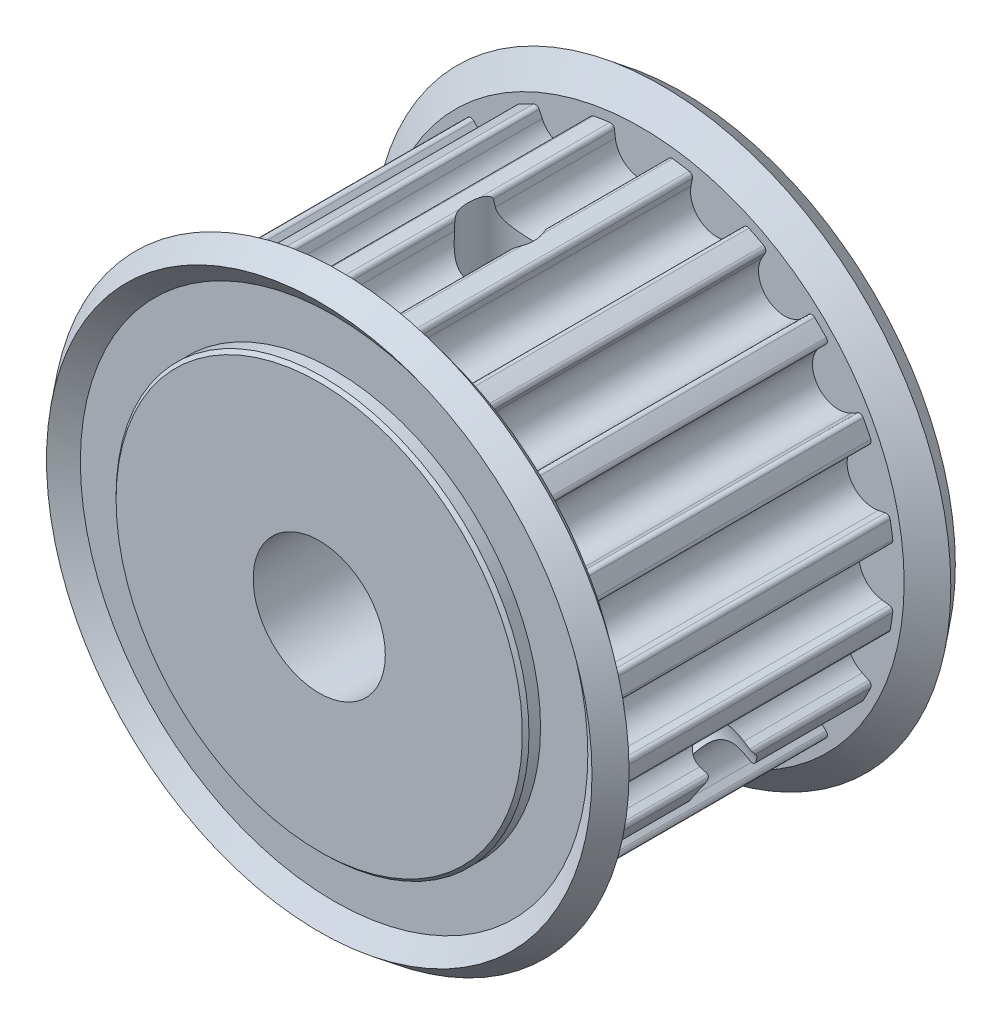
SolidWorks part; units mm, degrees
ref_plane "前视基准面" through (0, 0, 0) normal (0, 0, 1) x (1, 0, 0)
ref_plane "上视基准面" through (0, 0, 0) normal (0, 1, 0) x (1, 0, 0)
ref_plane "右视基准面" through (0, 0, 0) normal (1, 0, 0) x (0, 0, -1)
sketch "草图1" plane through (0, 0, 0) normal (1, 0, 0) x (0, 0, -1)
  line L0 (-34.7811, 0) -> (33.6192, 0) construction
  line L1 (0, 52.9736) -> (0, -62.0281) construction
  line L2 (-8.5, 15.345) -> (-8.5, 15.915)
  line L3 (-8.5, 15.915) -> (-9.7397, 17.5)
  line L4 (-9.7397, 17.5) -> (-11, 16.5143)
  line L5 (-11, 16.5143) -> (-10.1, 15.3636)
  line L6 (-10.1, 15.3636) -> (-10.1, 12.5)
  line L7 (-10.1, 12.5) -> (-11, 12.5)
  line L8 (10.1, 12.5) -> (11, 12.5)
  line L9 (10.1, 15.3636) -> (10.1, 12.5)
  line L10 (11, 16.5143) -> (10.1, 15.3636)
  line L11 (9.7397, 17.5) -> (11, 16.5143)
  line L12 (8.5, 15.915) -> (9.7397, 17.5)
  line L13 (8.5, 15.345) -> (8.5, 15.915)
  line L14 (8.5, -15.345) -> (8.5, -15.915)
  line L15 (8.5, -15.915) -> (9.7397, -17.5)
  line L16 (9.7397, -17.5) -> (11, -16.5143)
  line L17 (11, -16.5143) -> (10.1, -15.3636)
  line L18 (10.1, -15.3636) -> (10.1, -12.5)
  line L19 (10.1, -12.5) -> (11, -12.5)
  line L20 (-10.1, -12.5) -> (-11, -12.5)
  line L21 (-10.1, -15.3636) -> (-10.1, -12.5)
  line L22 (-11, -16.5143) -> (-10.1, -15.3636)
  line L23 (-9.7397, -17.5) -> (-11, -16.5143)
  line L24 (-8.5, -15.915) -> (-9.7397, -17.5)
  line L25 (-8.5, -15.345) -> (-8.5, -15.915)
  line L26 (-11, 12.5) -> (-11, -12.5)
  line L27 (11, 12.5) -> (11, -12.5)
  line L28 (-8.5, 15.345) -> (8.5, 15.345)
  line L29 (-8.5, -15.345) -> (8.5, -15.345)
  point P33 (0, 15.345)
  dimension "D1" = 2.5
  dimension "F" = 35
  dimension "D2" = 1.6
  dimension "E" = 25
  dimension "D3" = 1.6
  dimension "W" = 22
  dimension "D4" = 31.83
  dimension "A" = 17
  dimension "D5" = 30.69
sketch "草图2" plane through (0, 0, 0) normal (0, 0, 1) x (1, 0, 0)
  line L0 (-18.7064, 0) -> (19.5832, 0) construction
  line L1 (0, 30.5033) -> (0, -25.8377) construction
  line L2 (0, 0) -> (0, 15.345) construction
  line L3 (1.5718, 14.5756) -> (1.625, 15.0088)
  line L7 (0, 52.9736) -> (0, -62.0281) construction
  line L8 (-1.5, 3.7081) -> (-1.5, 5.4)
  line L9 (1.5, 3.7081) -> (1.5, 5.4)
  line L10 (-1.5, 5.4) -> (1.5, 5.4)
  line L11 (-1.5718, 14.5756) -> (-1.625, 15.0088)
  circle A0 centre (0, 0) radius 15.345
  circle A1 centre (0, 0) radius 15.915 construction
  circle A6 centre (0, 0) radius 2.5
  circle A7 centre (0, 0) radius 4
  arc A11 (-1.5718, 14.5756) -> (1.5718, 14.5756) centre (0, 14.7686) ccw
  arc A12 (-1.625, 15.0088) -> (-1.9042, 15.2264) centre (-1.8731, 14.9783) ccw
  arc A13 (1.625, 15.0088) -> (1.9042, 15.2264) centre (1.8731, 14.9783) cw
  point P7 (0, 15.915)
  point P8 (0, 15.345)
  point P13 (15.345, 0)
  dimension "PD" = 31.83
  dimension "OD" = 30.69
  dimension "H" = 5
  dimension "N" = 8
  dimension "D3" = 0.5
  dimension "D4" = 2.16
  dimension "D5" = 3.25
  dimension "D1" = 7
  dimension "b" = 3
  dimension "t" = 1.4
sketch "草图3" plane through (0, 0, 0) normal (1, 0, 0) x (0, 0, -1)
  line L0 (-11, 12.5) -> (-11, -12.5) construction
  line L1 (11, 12.5) -> (11, -12.5) construction
  line L2 (11, 16.5143) -> (10.1, 15.3636) construction
  line L3 (10.1, 12.5) -> (11, 12.5) construction
  line L4 (10.1, 15.3636) -> (10.1, 12.5) construction
  line L5 (-10.1, 15.3636) -> (-10.1, 12.5) construction
  line L6 (-11, 12.5) -> (-11, 0)
  line L7 (11, 12.5) -> (11, 0)
  line L8 (9.7397, 17.5) -> (11, 16.5143) construction
  line L9 (10.1, 12.5) -> (11, 12.5)
  line L10 (10.1, 15.3636) -> (10.1, 12.5)
  line L11 (-10.1, 15.3636) -> (-10.1, 12.5)
  line L12 (8.5, 15.915) -> (9.7397, 17.5) construction
  line L13 (8.5, 15.345) -> (8.5, 15.915) construction
  line L14 (-8.5, 15.345) -> (8.5, 15.345) construction
  line L15 (-8.5, 15.345) -> (-8.5, 15.915) construction
  line L16 (-8.5, 15.915) -> (-9.7397, 17.5) construction
  line L17 (-9.7397, 17.5) -> (-11, 16.5143) construction
  line L18 (-11, 16.5143) -> (-10.1, 15.3636) construction
  line L19 (11, 16.5143) -> (10.1, 15.3636)
  line L20 (9.7397, 17.5) -> (11, 16.5143)
  line L21 (8.5, 15.915) -> (9.7397, 17.5)
  line L22 (8.5, 15.345) -> (8.5, 15.915)
  line L23 (-8.5, 15.345) -> (8.5, 15.345)
  line L24 (-8.5, 15.345) -> (-8.5, 15.915)
  line L25 (-8.5, 15.915) -> (-9.7397, 17.5)
  line L26 (-9.7397, 17.5) -> (-11, 16.5143)
  line L27 (-11, 16.5143) -> (-10.1, 15.3636)
  line L28 (-34.7811, 0) -> (33.6192, 0) construction
  line L29 (-34.7811, 0) -> (33.6192, 0) construction
  line L30 (-11, 0) -> (11, 0)
  line L31 (-10.1, 12.5) -> (-11, 12.5) construction
  line L32 (-10.1, 12.5) -> (-11, 12.5)
revolve "旋转1" add sketch "草图3" angle 360 about L29
sketch "草图4" plane through (0, 0, 0) normal (0, 0, 1) x (1, 0, 0)
  line L3 (-1.5718, 14.5756) -> (-1.625, 15.0088) construction
  line L4 (1.5718, 14.5756) -> (1.625, 15.0088) construction
  line L5 (-1.5718, 14.5756) -> (-1.625, 15.0088)
  line L6 (1.5718, 14.5756) -> (1.625, 15.0088)
  arc A5 (-1.625, 15.0088) -> (-1.9042, 15.2264) centre (-1.8731, 14.9783) ccw construction
  arc A6 (-1.5718, 14.5756) -> (1.5718, 14.5756) centre (0, 14.7686) ccw construction
  arc A7 (1.9042, 15.2264) -> (1.625, 15.0088) centre (1.8731, 14.9783) ccw construction
  circle A8 centre (0, 0) radius 15.345 construction
  arc A9 (-1.625, 15.0088) -> (-1.9042, 15.2264) centre (-1.8731, 14.9783) ccw
  arc A10 (-1.5718, 14.5756) -> (1.5718, 14.5756) centre (0, 14.7686) ccw
  arc A11 (1.9042, 15.2264) -> (1.625, 15.0088) centre (1.8731, 14.9783) ccw
  arc A12 (1.9042, 15.2264) -> (-1.9042, 15.2264) centre (0, 0) ccw
extrude "切除-拉伸1" cut sketch "草图4" along normal up to vertex (8.5 mm away) from vertex up to point (0, 15.345, 8.5) starting at point (0, 15.345, -8.5)
pattern_circular "阵列(圆周)1" count 20 over 360 about axis through (0, 0, 34.7811) along (0, 0, 1) of "切除-拉伸1"
sketch "草图5" plane through (0, 0, 0) normal (0, 0, 1) x (1, 0, 0)
  circle A0 centre (0, 0) radius 2.5 construction
  circle A1 centre (0, 0) radius 2.5
extrude "H" [suppressed] cut sketch "草图5" along normal up to vertex from vertex up to point (0, 12.5, 11) starting at point (0, 12.5, -11)
sketch "草图6" plane through (0, 0, 0) normal (0, 0, 1) x (1, 0, 0)
  line L0 (-1.5, 5.4) -> (1.5, 5.4) construction
  line L1 (1.5, 3.7081) -> (1.5, 5.4) construction
  line L2 (-1.5, 3.7081) -> (-1.5, 5.4) construction
  line L3 (-1.5, 5.4) -> (1.5, 5.4)
  line L4 (1.5, 3.7081) -> (1.5, 5.4)
  line L5 (-1.5, 3.7081) -> (-1.5, 5.4)
  circle A0 centre (0, 0) radius 4 construction
  arc A1 (-1.5, 3.7081) -> (1.5, 3.7081) centre (0, 0) ccw
extrude "N" cut sketch "草图6" along normal up to vertex (11 mm away) from vertex up to point (0, 12.5, 11) starting at point (0, 12.5, -11)
sketch "草图8" plane through (0, 0, 0) normal (0, 0, 1) x (1, 0, 0)
  line L0 (-1.5, 3.7081) -> (-1.5, 5.4) construction
  line L1 (-1.5, 5.4) -> (1.5, 5.4) construction
  line L2 (1.5, 3.7081) -> (1.5, 5.4) construction
  line L3 (-1.5, 3.7081) -> (-1.5, 5.4)
  line L4 (-1.5, 5.4) -> (1.5, 5.4)
  line L5 (1.5, 3.7081) -> (1.5, 5.4)
  circle A0 centre (0, 0) radius 4 construction
  arc A1 (1.5, 3.7081) -> (-1.5, 3.7081) centre (0, 0) ccw
extrude "P" add sketch "草图8" against normal up to vertex from vertex up to point (0, 12.5, -11) starting at point (0, 12.5, 11)
sketch "草图7" plane through (0, 0, 0) normal (0, 1, 0) x (1, 0, 0)
  circle A0 centre (0, 0) radius 2
  dimension "M" = 4
extrude "螺纹孔1" cut sketch "草图7" along normal up to vertex up to point (0, 15.345, 0)
cosmetic thread "装饰螺纹线1" parameters "D2"=4.1
pattern_circular "螺纹孔2" count 2 every 120 about axis through (0, 0, 34.7811) along (0, 0, 1) of "螺纹孔1" reverse direction yes
chamfer "倒角1" distance 0.2 angle 45 2 edges at (12.5, 0, -11) (12.5, 0, 11)
